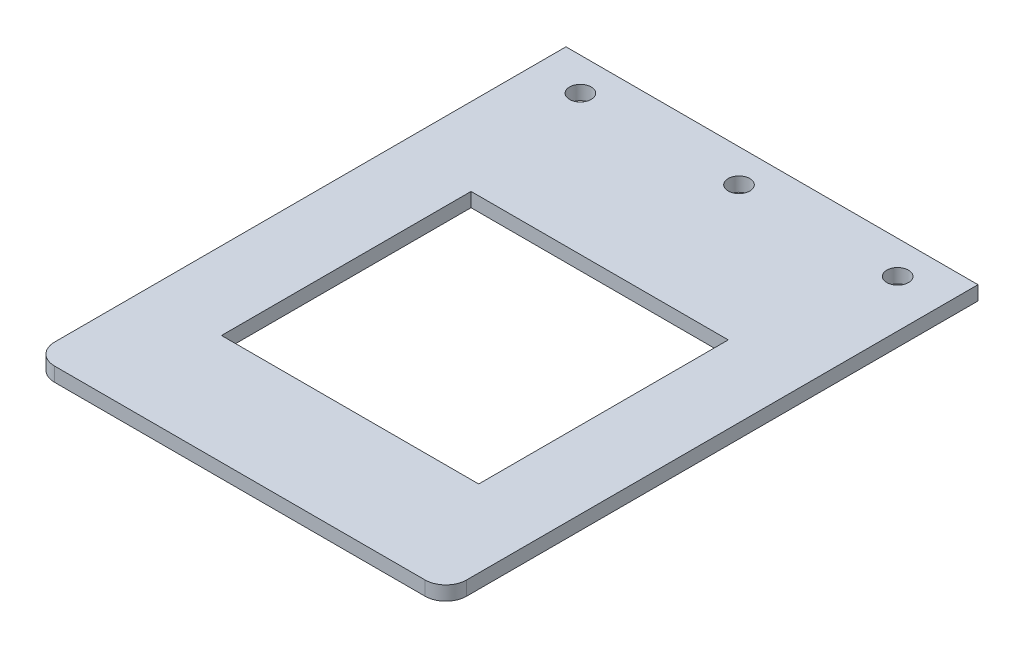
SolidWorks part; units mm, degrees
ref_plane "Front Plane" through (0, 0, 0) normal (0, 0, 1) x (1, 0, 0)
ref_plane "Top Plane" through (0, 0, 0) normal (0, 1, 0) x (1, 0, 0)
ref_plane "Right Plane" through (0, 0, 0) normal (1, 0, 0) x (0, 0, -1)
sketch "Sketch1" plane through (0, 0, 0) normal (0, 1, 0) x (1, 0, 0)
  line L10 (-16.9379, -16.3429) -> (10.3671, -16.3429)
  line L11 (10.3671, -16.3429) -> (10.3671, 10.1491)
  line L12 (10.3671, 10.1491) -> (-16.9379, 10.1491)
  line L13 (-16.9379, 10.1491) -> (-16.9379, -16.3429)
  line L16 (-14.2871, 14.6854) -> (12.9539, 14.6854)
  line L17 (12.9539, 14.6854) -> (12.9539, 18.4324)
  line L18 (12.9539, 18.4324) -> (-14.2871, 18.4324)
  line L19 (-14.2871, 18.4324) -> (-14.2871, 14.6854)
  line L22 (-25.1937, -23.3118) -> (-25.1937, 28.4832)
  line L23 (18.5453, 28.4832) -> (18.5453, -23.3118)
  line L24 (-25.1937, 28.4832) -> (18.5453, 28.4832)
  line L25 (18.5453, -23.3118) -> (18.5453, -24.5118)
  line L26 (-25.1937, -23.3118) -> (-25.1937, -24.5118)
  line L27 (18.5453, -24.5118) -> (18.5453, -25.8118)
  line L30 (-25.1937, -24.5118) -> (-25.1937, -25.8118)
  line L32 (-22.9937, -28.0118) -> (16.3453, -28.0118)
  circle A0 centre (-20.1649, 24.9832) radius 1.15
  circle A1 centre (-3.3249, 24.9832) radius 1.15
  circle A2 centre (13.5151, 24.9832) radius 1.15
  arc A7 (18.5453, -25.8118) -> (16.3453, -28.0118) centre (16.3453, -25.8118) cw
  arc A8 (-25.1937, -25.8118) -> (-22.9937, -28.0118) centre (-22.9937, -25.8118) ccw
extrude "Boss-Extrude1" add sketch "Sketch1" along normal blind 1.5
sketch "Sketch2" plane through (0, 1.5, 0) normal (0, 1, 0) x (1, 0, 0)
  line L0 (-14.2871, 18.4324) -> (12.9539, 18.4324)
  line L1 (12.9539, 18.4324) -> (12.9539, 14.6854)
  line L2 (12.9539, 14.6854) -> (-14.2871, 14.6854)
  line L3 (-14.2871, 14.6854) -> (-14.2871, 18.4324)
  line L4 (18.5453, 28.4832) -> (-25.1937, 28.4832)
  line L5 (-25.1937, 28.4832) -> (-25.1937, -25.8118)
  line L6 (-22.9937, -28.0118) -> (16.3453, -28.0118)
  line L7 (18.5453, -25.8118) -> (18.5453, 28.4832)
  line L8 (18.5453, 28.4832) -> (-25.1937, 28.4832)
  line L9 (-25.1937, 28.4832) -> (-25.1937, -25.8118)
  line L11 (18.5453, -25.8118) -> (18.5453, 28.4832)
  line L17 (-22.9937, -28.0118) -> (16.3453, -28.0118)
  arc A2 (-25.1937, -25.8118) -> (-22.9937, -28.0118) centre (-22.9937, -25.8118) ccw
  arc A6 (-25.1937, -25.8118) -> (-22.9937, -28.0118) centre (-22.9937, -25.8118) ccw
  arc A8 (16.3453, -28.0118) -> (18.5453, -25.8118) centre (16.3453, -25.8118) ccw
  arc A9 (16.3453, -28.0118) -> (18.5453, -25.8118) centre (16.3453, -25.8118) ccw
  dimension "D1" = 0
extrude "Boss-Extrude2" add sketch "Sketch2" along normal blind 2 separate body contours L3 L0 L1 L2
sketch "Sketch3" plane through (0, 1.5, 0) normal (0, -1, 0) x (1, 0, 0)
  line L4 (12.9539, -14.6854) -> (-14.2871, -14.6854)
  line L5 (-14.2871, -14.6854) -> (-14.2871, -18.4324)
  line L6 (-14.2871, -18.4324) -> (12.9539, -18.4324)
  line L7 (12.9539, -18.4324) -> (12.9539, -14.6854)
  line L8 (12.9539, -14.6854) -> (-14.2871, -14.6854)
  line L9 (-14.2871, -14.6854) -> (-14.2871, -18.4324)
  line L10 (-14.2871, -18.4324) -> (12.9539, -18.4324)
  line L11 (12.9539, -18.4324) -> (12.9539, -14.6854)
  dimension "D1" = 0
extrude "Boss-Extrude3" add sketch "Sketch3" along normal up to surface (1.5 mm away) up to face at (-3.3249, 0, -23.8332)
sketch "Sketch5" plane through (0, 0, 0) normal (0, -1, 0) x (1, 0, 0)
  line L0 (-14.2871, -18.4324) -> (-9.2871, -18.4324)
  line L1 (-9.2871, -18.4324) -> (-9.2871, -14.6854)
  line L2 (12.9539, -18.4324) -> (7.9539, -18.4324)
  line L3 (7.9539, -18.4324) -> (7.9539, -14.6854)
  line L4 (12.9539, -14.6854) -> (-14.2871, -14.6854)
  line L5 (12.9539, -18.4324) -> (12.9539, -14.6854)
  line L6 (-14.2871, -18.4324) -> (12.9539, -18.4324)
  line L7 (-14.2871, -14.6854) -> (-14.2871, -18.4324)
  line L8 (12.9539, -14.6854) -> (-14.2871, -14.6854)
  line L9 (12.9539, -18.4324) -> (12.9539, -14.6854)
  line L10 (-14.2871, -18.4324) -> (12.9539, -18.4324)
  line L11 (-14.2871, -14.6854) -> (-14.2871, -18.4324)
  line L12 (7.9539, -14.6854) -> (-9.2871, -14.6854)
  line L13 (-9.2871, -18.4324) -> (7.9539, -18.4324)
  dimension "D1" = 0
extrude "Boss-Extrude4" add sketch "Sketch5" along normal blind 2 contours L1 L10 L3 L8 region at (-0.6666, 0, -16.5589)
sketch "Sketch6" plane through (0, 3.5, 0) normal (0, 1, 0) x (1, 0, 0)
  line L4 (-14.2871, 14.6854) -> (12.9539, 14.6854)
  line L5 (12.9539, 14.6854) -> (12.9539, 18.4324)
  line L6 (12.9539, 18.4324) -> (-14.2871, 18.4324)
  line L7 (-14.2871, 18.4324) -> (-14.2871, 14.6854)
  line L8 (-14.2871, 14.6854) -> (12.9539, 14.6854)
  line L9 (12.9539, 14.6854) -> (12.9539, 18.4324)
  line L10 (12.9539, 18.4324) -> (-14.2871, 18.4324)
  line L11 (-14.2871, 18.4324) -> (-14.2871, 14.6854)
  dimension "D1" = 0
extrude "Cut-Extrude1" cut sketch "Sketch6" against normal up to surface (2 mm away) up to face at (-0.6666, 1.5, -16.5589)
